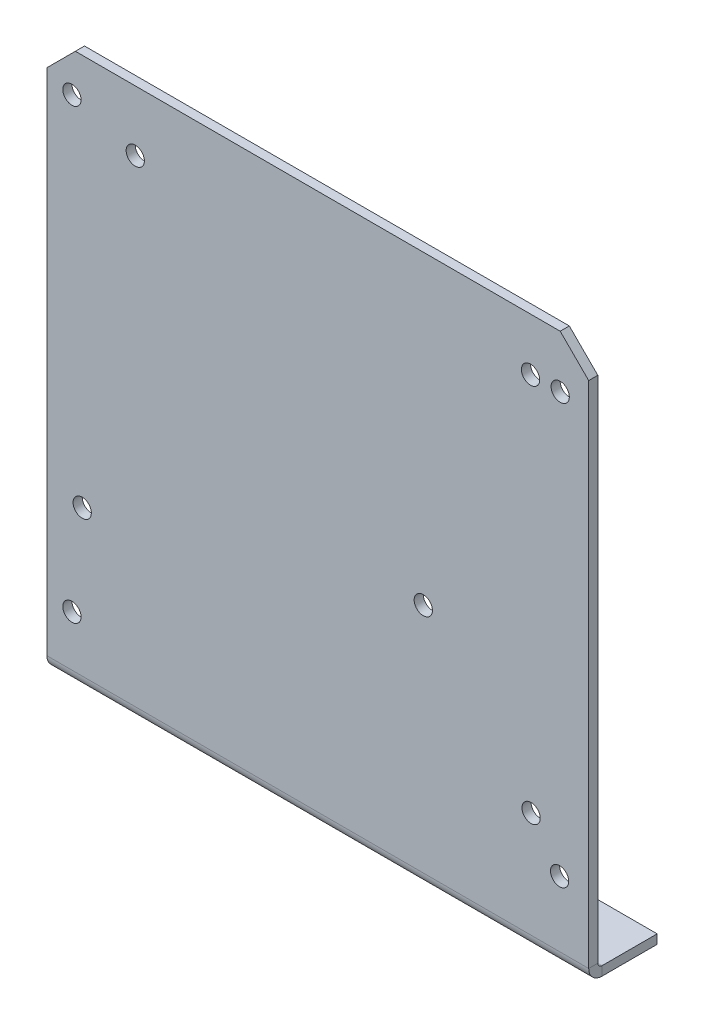
SolidWorks part; units mm, degrees
note: The reader was unsure of these and kept them because the rebuilt part matched: flange length of "边线-法兰2".
ref_plane "前视基准面" through (0, 0, 0) normal (0, 0, 1) x (1, 0, 0)
ref_plane "上视基准面" through (0, 0, 0) normal (0, 1, 0) x (1, 0, 0)
ref_plane "右视基准面" through (0, 0, 0) normal (1, 0, 0) x (0, 0, -1)
sketch "草图1" plane through (0, 0, 0) normal (0, 0, 1) x (1, 0, 0)
  line L0 (-140.9906, 0) -> (134.6908, 0) construction
  line L1 (0, 103.1915) -> (0, -106.2155) construction
  line L2 (-47.5, 42.5) -> (-42.5, 47.5)
  line L3 (47.5, -47.5) -> (-47.5, -47.5)
  line L4 (47.5, -47.5) -> (47.5, 42.5)
  line L5 (42.5, 47.5) -> (-42.5, 47.5)
  line L6 (-47.5, -47.5) -> (-47.5, 42.5)
  line L7 (47.5, -47.5) -> (-45, 45) construction
  line L8 (45, 45) -> (-47.5, -47.5) construction
  line L9 (42.5, 47.5) -> (47.5, 42.5)
  point P5 (0, 0)
  dimension "D1" = 95
  dimension "D2" = 95
sheet metal parameters "钣金2" thickness 1.6 parameters "D1"=0.7366
base flange "基体-法兰2" sketch "草图1" thickness 1.6 reverse thickness direction no parameters "D1"=0.7366
edge flange "边线-法兰2" sketch "草图13" flange angle 90 flange length 12 flange position material outside bend radius 0.7366 thickness 1.6 relief rectangular parameters "D6"=10
sketch "草图13" plane through (0, -47.5, -1.6) normal (0, -1, 0) x (-1, 0, 0)
  line L0 (47.5, 0) -> (-47.5, 0) construction
  line L1 (47.5, 0) -> (-47.5, 0)
  line L2 (-47.5, 0) -> (-47.5, 10.4)
  line L3 (-47.5, 10.4) -> (47.5, 10.4)
  line L4 (47.5, 10.4) -> (47.5, 0)
bend "边线折弯2" bend radius 0.7366 bend angle 90 parameters "D5"=1
sketch "草图16" plane through (0, -47.5, 0) normal (0, 1, 0) x (1, 0, 0)
  line L0 (-47.5, 12) -> (47.5, 12) construction
  line L1 (-47.5, 2.3366) -> (-47.5, 12) construction
  circle A0 centre (-30, 7) radius 4.05
  dimension "D3" = 8.1
  dimension "D1" = 5
  dimension "D2" = 17.5
extrude "凸台-拉伸1" add sketch "草图16" along normal blind 1.9
sketch "草图17" plane through (0, -45.6, 0) normal (0, 1, 0) x (1, 0, 0)
  circle A0 centre (-30, 7) radius 1.6
  dimension "D1" = 3.2
extrude "切除-拉伸1" cut sketch "草图17" against normal through all normal cut yes
mirror "镜向1" about plane through (0, 0, 0) normal (1, 0, 0) of "凸台-拉伸1", "切除-拉伸1"
sketch "草图18" plane through (0, 0, -1.6) normal (0, 0, -1) x (-1, 0, 0)
  line L5 (-42.5, 47.5) -> (42.5, 47.5) construction
  line L6 (-47.5, -46.7634) -> (-47.5, 42.5) construction
  line L7 (-42.5, 38.3) -> (-37.3, 38.3) construction
  line L8 (47.5, 42.5) -> (47.5, -46.7634) construction
  line L9 (47.5, -49.1) -> (-47.5, -49.1) construction
  circle A0 centre (-42.5, 38.3) radius 1.6
  circle A1 centre (32, 36.9) radius 1.6
  circle A2 centre (43.1, 40.6) radius 1.6
  circle A3 centre (-18.5, -6.1) radius 1.6
  circle A4 centre (-37.4, -28.2) radius 1.6
  circle A5 centre (-42.4, -35.3) radius 1.6
  circle A6 centre (41.3, -21.2) radius 1.6
  circle A7 centre (43.1, -37.9) radius 1.6
  circle A8 centre (-37.3, 38.3) radius 1.6
  dimension "D3" = 3.2
  dimension "D8" = 3.2
  dimension "D9" = 3.2
  dimension "D10" = 3.2
  dimension "D11" = 3.2
  dimension "D12" = 3.2
  dimension "D13" = 3.2
  dimension "D14" = 3.2
  dimension "D1" = 9.2
  dimension "D2" = 5
  dimension "D5" = 5.2
  dimension "D6" = 4.4
  dimension "D7" = 6.9
  dimension "D15" = 15.5
  dimension "D16" = 10.6
  dimension "D17" = 29
  dimension "D18" = 53.6
  dimension "D19" = 5.1
  dimension "D20" = 13.8
  dimension "D21" = 10.1
  dimension "D22" = 20.9
  dimension "D23" = 6.2
  dimension "D24" = 27.9
  dimension "D25" = 4.4
  dimension "D26" = 11.2
  dimension "D4" = 2
extrude "切除-拉伸2" cut sketch "草图18" against normal through all normal cut yes
flat pattern "平板型式2" [suppressed]
sketch "折弯-线2" plane through (0, 0, 0) normal (0, 1, 0) x (-1, 0, 0)
sketch "边界框2" [suppressed] plane through (0, 0, 0) normal (0, 1, 0) x (-1, 0, 0)
bend of the flat pattern "展开-<边线折弯2>1"
